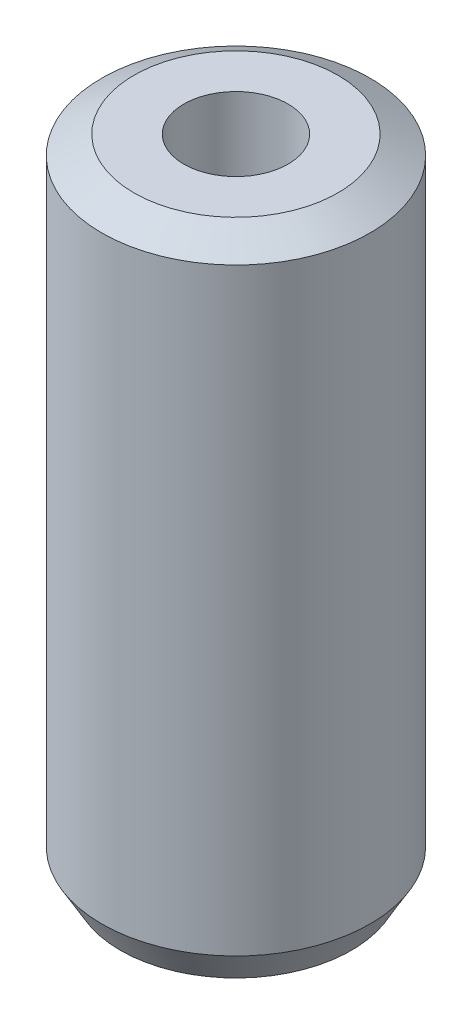
SolidWorks part; units mm, degrees
ref_plane "Front Plane" through (0, 0, 0) normal (0, 0, 1) x (1, 0, 0)
ref_plane "Top Plane" through (0, 0, 0) normal (0, 1, 0) x (1, 0, 0)
ref_plane "Right Plane" through (0, 0, 0) normal (1, 0, 0) x (0, 0, -1)
sketch "Sketch1" plane through (0, 0, 0) normal (0, 1, 0) x (1, 0, 0)
  circle A0 centre (0, 0) radius 42.5
  dimension "SHAFT_OD" = 85
extrude "Boss-Extrude1" add sketch "Sketch1" along normal blind 205.681
sketch "Sketch2" plane through (0, 0, 0) normal (0, 1, 0) x (1, 0, 0)
  circle A0 centre (0, 0) radius 16.5151
  dimension "BORE_D" = 33.0302
extrude "Cut-Extrude1" cut sketch "Sketch2" along normal through all
chamfer "Chamfer1" distance 5.8856 angle 60 2 edges at (0, 205.681, 42.5) (0, 0, 42.5) first distance on face at (0, 205.681, 42.5) first distance on face at (0, 0, 16.5151)
